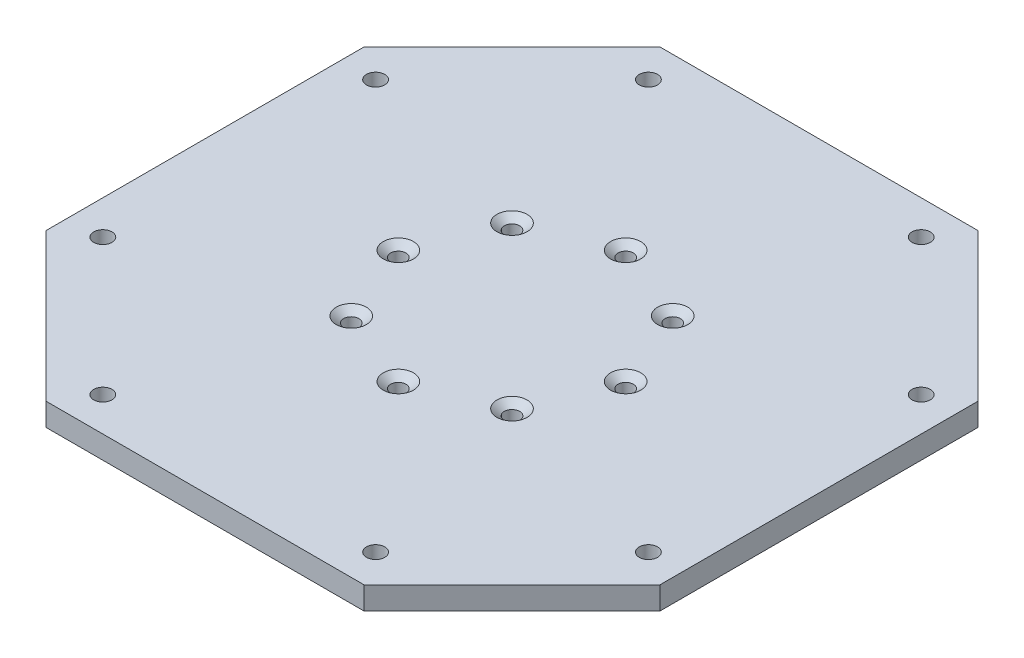
SolidWorks part; units mm, degrees
ref_plane "Front Plane" through (0, 0, 0) normal (0, 0, 1) x (1, 0, 0)
ref_plane "Top Plane" through (0, 0, 0) normal (0, 1, 0) x (1, 0, 0)
ref_plane "Right Plane" through (0, 0, 0) normal (1, 0, 0) x (0, 0, -1)
sketch "Sketch1" plane through (0, 0, 0) normal (0, 1, 0) x (1, 0, 0)
  line L0 (-85.725, 44.45) -> (-44.45, 85.725)
  line L1 (-44.45, -85.725) -> (44.45, -85.725)
  line L2 (-85.725, -44.45) -> (-85.725, 44.45)
  line L3 (-44.45, 85.725) -> (44.45, 85.725)
  line L4 (85.725, -44.45) -> (85.725, 44.45)
  line L5 (-85.725, -85.725) -> (85.725, 85.725) construction
  line L6 (-85.725, 85.725) -> (85.725, -85.725) construction
  line L7 (44.45, 85.725) -> (85.725, 44.45)
  line L8 (85.725, -44.45) -> (44.45, -85.725)
  line L9 (-85.725, -44.45) -> (-44.45, -85.725)
  point P0 (0, 0)
  dimension "D1" = 171.45
  dimension "D2" = 171.45
  dimension "D3" = 88.9
extrude "Boss-Extrude1" add sketch "Sketch1" along normal blind 6.35
hole_wizard "#7 (0.201) Diameter Hole1" positions "Sketch3" profile "Sketch2" hole size "#7" standard "Ansi Inch" end condition through all
sketch "Sketch3" plane through (0, 6.35, 0) normal (0, 1, 0) x (-1, 0, 0)
  line L0 (-38.1, -76.2) -> (0, 0) construction
  line L1 (0, 0) -> (38.1, -76.2) construction
  line L4 (-44.45, -85.725) -> (44.45, -85.725) construction
  point P0 (38.1, -76.2)
  point P1 (-38.1, -76.2)
  dimension "D1" = 76.2
  dimension "D2" = 9.525
sketch "Sketch2" plane through (-38.1, 6.35, -76.2) normal (1, 0, 0) x (0, 0, 1)
  line L0 (0, 0) -> (0, 6.35)
  line L1 (0, 6.35) -> (2.5527, 6.35)
  line L2 (2.5527, 6.35) -> (2.5527, 0)
  line L5 (2.5527, 0) -> (0, 0)
  line L11 (0, -6.35) -> (0, 107.95) construction
  dimension "Thru Hole Dia." = 5.1054
  dimension "Thru Hole Depth" = 6.35
ref_axis "Axis1" through (0, 0, 0) along (0, 1, 0)
pattern_circular "CirPattern1" count 4 over 360 about axis through (0, 0, 0) along (0, 1, 0) of "#7 (0.201) Diameter Hole1"
hole_wizard "CSK for #8 Flat Head Machine Screw (100)1" positions "Sketch5" profile "Sketch4" countersink size "#8" standard "Ansi Inch" end condition through all
sketch "Sketch5" plane through (0, 6.35, 0) normal (0, 1, 0) x (-1, 0, 0)
  point P0 (0, 31.75)
  dimension "D1" = 31.75
sketch "Sketch4" plane through (0, 6.35, 31.75) normal (1, 0, 0) x (0, 0, 1)
  line L0 (0, 0) -> (0, 6.35)
  line L1 (0, 6.35) -> (2.1526, 6.35)
  line L2 (2.1526, 6.35) -> (2.1526, 1.7317)
  line L3 (2.1526, 1.7317) -> (4.2164, 0)
  line L5 (4.2164, 0) -> (0, 0)
  line L6 (-2.1526, 1.7317) -> (-4.2164, 0) construction
  line L11 (0, -6.35) -> (0, 107.95) construction
  dimension "Thru Hole Dia." = 4.3053
  dimension "Thru Hole Depth" = 6.35
  dimension "Near C'Sink Dia." = 8.4328
  dimension "Near C'Sink Angle" = 100
pattern_circular "CirPattern2" count 8 over 360 about axis through (0, 0, 0) along (0, 1, 0) of "CSK for #8 Flat Head Machine Screw (100)1"
